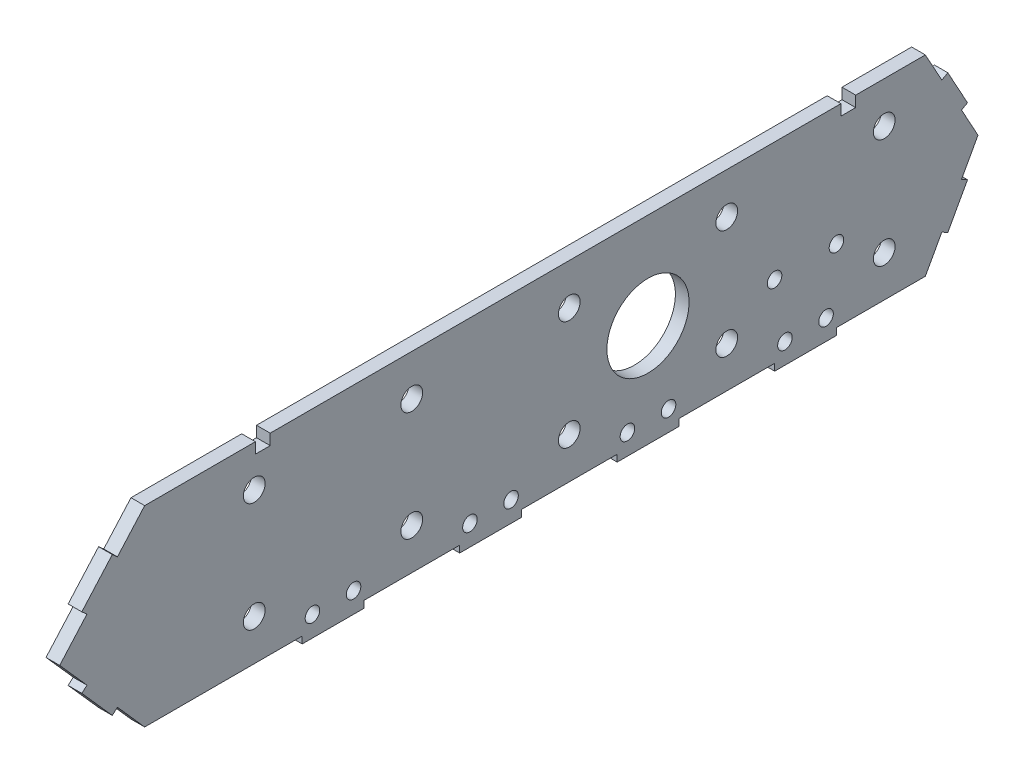
SolidWorks part; units mm, degrees
material "Plain Carbon Steel"
ref_plane "Front Plane" through (0, 0, 0) normal (0, 0, 1) x (1, 0, 0)
ref_plane "Top Plane" through (0, 0, 0) normal (0, 1, 0) x (1, 0, 0)
ref_plane "Right Plane" through (0, 0, 0) normal (1, 0, 0) x (0, 0, -1)
sketch "Sketch1" plane through (0, 0, 0) normal (1, 0, 0) x (0, 0, -1)
  line L0 (0, 44.45) -> (0, 0) construction
  line L1 (-279.4, 44.45) -> (279.4, 44.45)
  line L2 (-279.4, 44.45) -> (-279.4, -44.45)
  line L3 (-279.4, -44.45) -> (279.4, -44.45)
  line L4 (279.4, 44.45) -> (279.4, -44.45)
  line L5 (0, 0) -> (279.4, 0) construction
  dimension "D1" = 558.8
  dimension "D2" = 88.9
extrude "Boss-Extrude1" add sketch "Sketch1" along normal blind 6.35 contours L4 L1 L2 L3 region at (0, 0, 0)
sketch "Sketch2" plane through (6.35, 0, 0) normal (1, 0, 0) x (0, 0, -1)
  line L0 (-279.4, 44.45) -> (-318.8009, 0)
  line L1 (-318.8009, 0) -> (-279.4, -44.45)
  line L2 (-279.4, -44.45) -> (-279.4, 44.45)
  line L3 (279.4, 44.45) -> (318.8009, 0)
  line L4 (318.8009, 0) -> (279.4, -44.45)
  line L5 (279.4, -44.45) -> (279.4, 44.45)
  line L6 (-318.8009, 0) -> (-226.9595, 103.6106) construction
  line L7 (-318.8009, 0) -> (-279.4, -44.45) construction
extrude "Boss-Extrude2" add sketch "Sketch2" against normal blind 6.35
hole_wizard "3/8 Clearance Hole2" positions "Sketch6" profile "Sketch5" hole size "3/8" standard "ANSI Inch" end condition through all
sketch "Sketch6" plane through (6.35, 0, 0) normal (1, 0, 0) x (0, 0, -1)
  line L0 (-279.4, 0) -> (-228.6, 25.4) construction
  line L1 (-228.6, 25.4) -> (-228.6, -25.4) construction
  line L2 (-228.6, -25.4) -> (-279.4, 0) construction
  line L5 (-155.575, -25.4) -> (-155.575, 25.4) construction
  line L8 (-228.6, 25.4) -> (-155.575, 25.4) construction
  line L9 (-155.575, 25.4) -> (-228.6, -25.4) construction
  line L10 (-228.6, -25.4) -> (-155.575, -25.4) construction
  line L11 (-155.575, -25.4) -> (-228.6, 25.4) construction
  point P6 (-155.575, -25.4)
  point P9 (-155.575, 25.4)
  point P12 (-228.6, 25.4)
  point P18 (-228.6, -25.4)
  dimension "D1" = 73.025
  dimension "D2" = 50.8
sketch "Sketch5" plane through (6.35, -25.4, 155.575) normal (0, 1, 0) x (0, 0, -1)
  line L0 (0, 0) -> (0, 6.35)
  line L1 (0, 6.35) -> (5.0419, 6.35)
  line L2 (5.0419, 6.35) -> (5.0419, 0)
  line L5 (5.0419, 0) -> (0, 0)
  line L11 (0, -6.35) -> (0, 107.95) construction
  dimension "Thru Hole Dia." = 10.0838
  dimension "Thru Hole Depth" = 6.35
hole_wizard "3/8 Clearance Hole3" positions "Sketch8" profile "Sketch7" hole size "3/8" standard "ANSI Inch"
sketch "Sketch8" plane through (0, 0, 0) normal (-1, 0, 0) x (0, 0, 1)
  point P0 (-63.5, 25.4)
  point P3 (-63.5, -25.4)
  point P6 (9.525, -25.4)
  point P9 (9.525, 25.4)
  point P12 (82.55, 25.4)
  point P15 (82.55, -25.4)
sketch "Sketch7" plane through (0, 25.4, -63.5) normal (0, 1, 0) x (0, 0, 1)
  line L0 (0, 0) -> (0, 15.7295)
  line L1 (0, 15.7295) -> (5.0419, 12.7)
  line L2 (5.0419, 12.7) -> (5.0419, 0)
  line L5 (5.0419, 0) -> (0, 0)
  line L10 (0, 15.7295) -> (-5.0419, 12.7) construction
  line L11 (0, -6.35) -> (0, 107.95) construction
  dimension "Hole Dia." = 10.0838
  dimension "Hole Depth" = 12.7
  dimension "Drill Angle" = 118
sketch "Sketch9" plane through (6.35, 0, 0) normal (1, 0, 0) x (0, 0, -1)
  line L0 (-279.4, 44.45) -> (279.4, 44.45) construction
  line L1 (82.55, 44.45) -> (322.0221, 44.45)
  line L2 (82.55, 44.45) -> (82.55, -44.45)
  line L3 (82.55, -44.45) -> (322.0221, -44.45)
  line L4 (322.0221, 44.45) -> (322.0221, -44.45)
extrude "Cut-Extrude1" cut sketch "Sketch9" against normal through all
sketch "Sketch10" plane through (6.35, 0, 0) normal (1, 0, 0) x (0, 0, -1)
  line L0 (82.55, -44.45) -> (106.9639, 0)
  line L1 (106.9639, 0) -> (82.55, 44.45)
  line L2 (82.55, 44.45) -> (82.55, -44.45)
extrude "Boss-Extrude3" add sketch "Sketch10" against normal blind 6.35
sketch "Sketch11" plane through (0, 0, 0) normal (-1, 0, 0) x (0, 0, 1)
  line L0 (-90.1924, 30.5356) -> (-92.9753, 32.0641)
  line L1 (-106.9639, 0) -> (-82.55, 44.45) construction
  line L2 (-92.9753, 32.0641) -> (-102.1044, 15.4428)
  line L3 (-102.1044, 15.4428) -> (-99.3215, 13.9144)
  line L4 (-99.3215, 13.9144) -> (-90.1924, 30.5356)
  line L5 (-99.3215, -13.9144) -> (-102.1044, -15.4428)
  line L6 (-82.55, -44.45) -> (-106.9639, 0) construction
  line L7 (-102.1044, -15.4428) -> (-92.9753, -32.0641)
  line L8 (-92.9753, -32.0641) -> (-90.1924, -30.5356)
  line L9 (-90.1924, -30.5356) -> (-99.3215, -13.9144)
  line L10 (292.0364, 30.1943) -> (294.4123, 32.3004)
  line L11 (279.4, 44.45) -> (318.8009, 0) construction
  line L12 (294.4123, 32.3004) -> (308.5405, 16.3617)
  line L13 (308.5405, 16.3617) -> (306.1645, 14.2557)
  line L14 (306.1645, 14.2557) -> (292.0364, 30.1943)
  line L15 (306.1645, -14.2557) -> (308.5405, -16.3617)
  line L16 (318.8009, 0) -> (279.4, -44.45) construction
  line L17 (308.5405, -16.3617) -> (294.4123, -32.3004)
  line L18 (294.4123, -32.3004) -> (292.0364, -30.1943)
  line L19 (292.0364, -30.1943) -> (306.1645, -14.2557)
  dimension "D1" = 3.175
  dimension "D2" = 15.875
  dimension "D3" = 15.875
  dimension "D4" = 15.875
  dimension "D5" = 15.875
  dimension "D6" = 19.05
  dimension "D7" = 19.05
  dimension "D8" = 19.05
  dimension "D9" = 19.05
extrude "Boss-Extrude4" add sketch "Sketch11" against normal blind 6.35
sketch "Sketch12" plane through (0, 0, 0) normal (-1, 0, 0) x (0, 0, 1)
  line L0 (9.525, 25.4) -> (82.55, 25.4) construction
  line L1 (82.55, 25.4) -> (82.55, -25.4) construction
  line L2 (82.55, -25.4) -> (9.525, -25.4) construction
  line L3 (9.525, -25.4) -> (9.525, 25.4) construction
  line L4 (9.525, 25.4) -> (82.55, -25.4) construction
  line L5 (9.525, -25.4) -> (82.55, 25.4) construction
  circle A0 centre (46.0375, 0) radius 19.05
  dimension "D1" = 38.1
extrude "Cut-Extrude2" cut sketch "Sketch12" against normal through all
sketch "Sketch13" plane through (0, 0, 0) normal (-1, 0, 0) x (0, 0, 1)
  line L0 (279.4, 44.45) -> (-82.55, 44.45) construction
  line L1 (-50.0062, 39.6875) -> (-43.6562, 39.6875)
  line L2 (-50.0062, 39.6875) -> (-50.0062, 44.45)
  line L3 (-50.0062, 44.45) -> (-43.6562, 44.45)
  line L4 (-43.6562, 39.6875) -> (-43.6562, 44.45)
  line L5 (221.2023, 39.4335) -> (221.2023, 44.704)
  line L6 (221.4563, 39.6875) -> (227.8063, 39.6875)
  line L7 (221.4563, 39.6875) -> (221.4563, 44.45)
  line L8 (221.4563, 44.45) -> (227.8063, 44.45)
  line L9 (227.8063, 39.6875) -> (227.8063, 44.45)
  line L10 (221.2023, 44.704) -> (228.0603, 44.704)
  line L11 (228.0603, 39.4335) -> (228.0603, 44.704)
  line L12 (221.2023, 39.4335) -> (228.0603, 39.4335)
  line L13 (-43.4022, 39.4335) -> (-43.4022, 44.704)
  line L14 (-50.2602, 44.704) -> (-43.4022, 44.704)
  line L15 (-50.2602, 39.4335) -> (-50.2602, 44.704)
  line L16 (-50.2602, 39.4335) -> (-43.4022, 39.4335)
  dimension "D1" = 0.254
extrude "Cut-Extrude3" cut sketch "Sketch13" against normal through all
hole_wizard "1/4 Clearance Hole1" positions "Sketch15" profile "Sketch14" hole size "1/4" standard "ANSI Inch" end condition through all
sketch "Sketch15" plane through (0, 0, 0) normal (-1, 0, 0) x (0, 0, 1)
  point P0 (-41.3385, -10.795)
  point P2 (-12.6365, -10.795)
sketch "Sketch14" plane through (0, -10.795, -41.3385) normal (0, 1, 0) x (0, 0, 1)
  line L0 (0, 0) -> (0, 6.35)
  line L1 (0, 6.35) -> (3.3782, 6.35)
  line L2 (3.3782, 6.35) -> (3.3782, 0)
  line L5 (3.3782, 0) -> (0, 0)
  line L11 (0, -6.35) -> (0, 107.95) construction
  dimension "Thru Hole Dia." = 6.7564
  dimension "Thru Hole Depth" = 6.35
hole_wizard "1/4 Clearance Hole2" positions "Sketch17" profile "Sketch16" hole size "1/4" standard "ANSI Inch" end condition through all
sketch "Sketch17" plane through (0, 0, 0) normal (-1, 0, 0) x (0, 0, 1)
  line L0 (-36.5125, -38.1) -> (-17.4625, -38.1) construction
  line L1 (-17.4625, -38.1) -> (36.5125, -38.1) construction
  line L2 (36.5125, -38.1) -> (55.5625, -38.1) construction
  line L3 (55.5625, -38.1) -> (109.5375, -38.1) construction
  line L4 (109.5375, -38.1) -> (128.5875, -38.1) construction
  line L5 (128.5875, -38.1) -> (182.5625, -38.1) construction
  line L6 (182.5625, -38.1) -> (201.6125, -38.1) construction
  line L7 (201.6125, -38.1) -> (228.6, -25.4) construction
  line L8 (228.6, -25.4) -> (155.575, -25.4) construction
  line L9 (155.575, -25.4) -> (82.55, -25.4) construction
  line L10 (82.55, -25.4) -> (9.525, -25.4) construction
  line L11 (9.525, -25.4) -> (-63.5, -25.4) construction
  line L12 (-63.5, -25.4) -> (-26.9875, -38.1) construction
  line L13 (-26.9875, -38.1) -> (-26.9875, -25.4) construction
  line L14 (-26.9875, -25.4) -> (46.0375, -38.1) construction
  line L15 (46.0375, -38.1) -> (46.0375, -25.4) construction
  line L16 (46.0375, -25.4) -> (119.0625, -38.1) construction
  line L17 (119.0625, -38.1) -> (119.0625, -25.4) construction
  line L18 (119.0625, -25.4) -> (192.0875, -38.1) construction
  line L19 (192.0875, -38.1) -> (192.0875, -25.4) construction
  line L21 (279.4, -44.45) -> (-82.55, -44.45) construction
  point P0 (-36.5125, -38.1)
  point P2 (-17.4625, -38.1)
  point P4 (36.5125, -38.1)
  point P6 (55.5625, -38.1)
  point P8 (109.5375, -38.1)
  point P10 (128.5875, -38.1)
  point P12 (182.5625, -38.1)
  point P14 (201.6125, -38.1)
  dimension "D1" = 19.05
  dimension "D2" = 6.35
sketch "Sketch16" plane through (0, -38.1, -36.5125) normal (0, 1, 0) x (0, 0, 1)
  line L0 (0, 0) -> (0, 6.35)
  line L1 (0, 6.35) -> (3.3782, 6.35)
  line L2 (3.3782, 6.35) -> (3.3782, 0)
  line L5 (3.3782, 0) -> (0, 0)
  line L11 (0, -6.35) -> (0, 107.95) construction
  dimension "Thru Hole Dia." = 6.7564
  dimension "Thru Hole Depth" = 6.35
sketch "Sketch18" plane through (0, 0, 0) normal (-1, 0, 0) x (0, 0, 1)
  line L0 (279.4, -44.45) -> (-82.55, -44.45) construction
  line L1 (-41.275, -44.45) -> (-12.7, -44.45)
  line L2 (-41.275, -44.45) -> (-41.275, -47.625)
  line L3 (-41.275, -47.625) -> (-12.7, -47.625)
  line L4 (-12.7, -44.45) -> (-12.7, -47.625)
  line L5 (31.75, -44.45) -> (60.325, -44.45)
  line L6 (31.75, -44.45) -> (31.75, -47.625)
  line L7 (31.75, -47.625) -> (60.325, -47.625)
  line L8 (60.325, -44.45) -> (60.325, -47.625)
  line L9 (104.775, -44.45) -> (133.35, -44.45)
  line L10 (104.775, -44.45) -> (104.775, -47.625)
  line L11 (104.775, -47.625) -> (133.35, -47.625)
  line L12 (133.35, -44.45) -> (133.35, -47.625)
  line L13 (177.8, -44.45) -> (206.375, -44.45)
  line L14 (177.8, -44.45) -> (177.8, -47.625)
  line L15 (177.8, -47.625) -> (206.375, -47.625)
  line L16 (206.375, -44.45) -> (206.375, -47.625)
  line L17 (-36.5125, -38.1) -> (-17.4625, -38.1) construction
  line L18 (-17.4625, -38.1) -> (36.5125, -38.1) construction
  line L19 (36.5125, -38.1) -> (55.5625, -38.1) construction
  line L20 (55.5625, -38.1) -> (109.5375, -38.1) construction
  line L21 (109.5375, -38.1) -> (128.5875, -38.1) construction
  line L22 (128.5875, -38.1) -> (182.5625, -38.1) construction
  line L23 (182.5625, -38.1) -> (201.6125, -38.1) construction
  line L25 (192.0875, -44.45) -> (192.0875, -38.1) construction
  line L27 (119.0625, -44.45) -> (119.0625, -38.1) construction
  line L29 (46.0375, -44.45) -> (46.0375, -38.1) construction
  line L31 (-26.9875, -44.45) -> (-26.9875, -38.1) construction
  circle A0 centre (-17.4625, -38.1) radius 3.3782 construction
  circle A1 centre (109.5375, -38.1) radius 3.3782 construction
  dimension "D1" = 3.175
  dimension "D2" = 28.575
extrude "Boss-Extrude5" add sketch "Sketch18" against normal up to surface (6.35 mm away) up to face at (6.35, -38.1, -33.1343)
